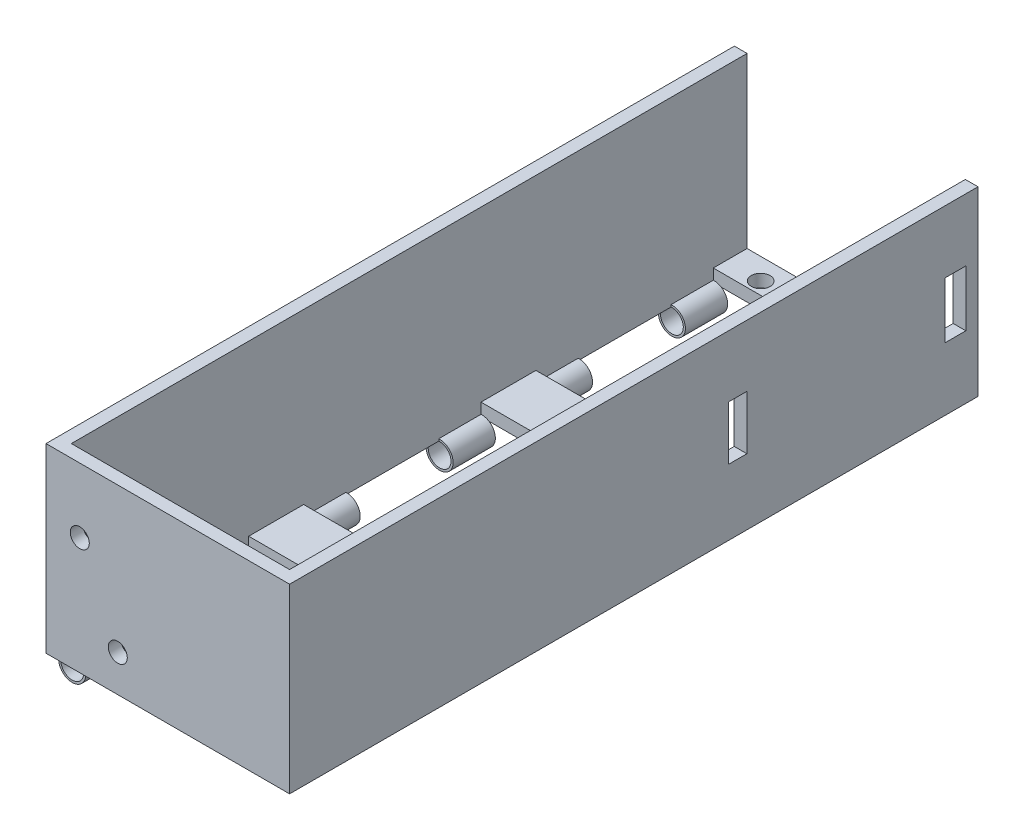
SolidWorks part; units mm, degrees
ref_plane "Front Plane" through (0, 0, 0) normal (0, 0, 1) x (1, 0, 0)
ref_plane "Top Plane" through (0, 0, 0) normal (0, 1, 0) x (1, 0, 0)
ref_plane "Right Plane" through (0, 0, 0) normal (1, 0, 0) x (0, 0, -1)
sketch "Sketch1" plane through (0, 0, 0) normal (0, 0, 1) x (1, 0, 0)
  line L0 (0, 0) -> (0, -10)
  line L1 (0, -10) -> (0, -40)
  line L2 (0, -40) -> (51.6786, -40)
  line L5 (-3, 0) -> (-3, -10)
  line L6 (-3, -10) -> (-3, -43)
  line L7 (-3, -43) -> (54.6786, -43)
  line L10 (-3, 0) -> (0, 0)
  line L12 (51.6786, -40) -> (51.6786, 0)
  line L13 (51.6786, -40) -> (51.6786, 37.6119) construction
  line L14 (51.6786, 37.6119) -> (67.0297, -2.1736) construction
  line L15 (54.6786, -43) -> (54.6786, 21.503) construction
  line L16 (54.6786, 21.503) -> (64.2308, -3.2535) construction
  line L17 (51.6786, 0) -> (54.6786, 0)
  line L18 (54.6786, 0) -> (54.6786, -43)
  dimension "D2" = 10
  dimension "D3" = 30
  dimension "D5" = 3
  dimension "D1" = 3
extrude "Boss-Extrude1" add sketch "Sketch1" along normal blind 160
sketch "Sketch2" plane through (0, 0, 0) normal (0, 1, 0) x (1, 0, 0)
  line L0 (51.6786, -160) -> (0, -160) construction
  line L1 (49, -8) -> (0, -8)
  line L2 (49, -8) -> (49, -50)
  line L3 (49, -50) -> (0, -50)
  line L4 (0, -8) -> (0, -50)
  line L5 (49, -63) -> (0, -63)
  line L6 (49, -63) -> (49, -105)
  line L7 (49, -105) -> (0, -105)
  line L8 (0, -63) -> (0, -105)
  line L9 (49, -118) -> (0, -118)
  line L10 (49, -118) -> (49, -160)
  line L11 (49, -160) -> (0, -160)
  line L12 (0, -118) -> (0, -160)
  line L13 (0, -160) -> (0, 0) construction
  dimension "D1" = 42
  dimension "D2" = 13
  dimension "D3" = 42
  dimension "D4" = 13
  dimension "D5" = 42
  dimension "D6" = 49
extrude "Cut-Extrude1" cut sketch "Sketch2" against normal through all
sketch "Sketch3" plane through (0, 0, 160) normal (0, 0, 1) x (1, 0, 0)
  line L0 (-3, 0) -> (54.6786, 0)
  line L1 (54.6786, 0) -> (54.6786, -43)
  line L2 (54.6786, -43) -> (0, -43)
  line L10 (0, 0) -> (-3, 0)
  line L11 (-3, 0) -> (-3, -43)
  line L13 (-3, -43) -> (0, -43)
  line L18 (0, -43) -> (0, 0)
  line L21 (-3, 0) -> (-3, -43)
  line L23 (-3, -43) -> (0, -43)
  dimension "D1" = 0
extrude "Boss-Extrude2" add sketch "Sketch3" along normal blind 3
sketch "Sketch4" plane through (0, 0, 163) normal (0, 0, 1) x (1, 0, 0)
  circle A0 centre (14, -34.2995) radius 2.25 construction
  circle A1 centre (5, -15.3106) radius 2.25 construction
  circle A2 centre (14, -34.2995) radius 2.25
  circle A3 centre (5, -15.3106) radius 2.25
extrude "Cut-Extrude2" cut sketch "Sketch4" against normal up to next
sketch "Sketch5" plane through (0, -40, 0) normal (0, 1, 0) x (1, 0, 0)
  line L14 (49, -8) -> (49, -50)
  line L15 (49, -50) -> (0, -50)
  line L16 (0, -50) -> (0, -63)
  line L17 (0, -63) -> (49, -63)
  line L18 (49, -63) -> (49, -105)
  line L19 (49, -105) -> (0, -105)
  line L20 (0, -105) -> (0, -118)
  line L21 (0, -118) -> (49, -118)
  line L22 (49, -118) -> (49, -160)
  line L23 (49, -160) -> (51.6786, -160)
  line L24 (51.6786, -160) -> (51.6786, 0)
  line L25 (51.6786, 0) -> (0, 0)
  line L26 (0, 0) -> (0, -8)
  line L27 (0, -8) -> (49, -8)
  line L28 (49, -8) -> (49, -50)
  line L29 (49, -50) -> (0, -50)
  line L30 (0, -50) -> (0, -63)
  line L31 (0, -63) -> (49, -63)
  line L32 (49, -63) -> (49, -105)
  line L33 (49, -105) -> (0, -105)
  line L34 (0, -105) -> (0, -118)
  line L35 (0, -118) -> (49, -118)
  line L36 (49, -118) -> (49, -160)
  line L37 (49, -160) -> (51.6786, -160)
  line L38 (51.6786, -160) -> (51.6786, 0)
  line L39 (51.6786, 0) -> (0, 0)
  line L40 (0, 0) -> (0, -8)
  line L41 (0, -8) -> (49, -8)
  ellipse E0 centre (8.2809, -5.054) end of major axis (6.0309, -5.054) minor radius 2.2278 construction
  ellipse E1 centre (8.2809, -5.054) end of major axis (6.0309, -5.054) minor radius 2.2278
  dimension "D1" = 0
extrude "Cut-Extrude3" cut sketch "Sketch5" against normal up to next contours E1 region at (8.2809, -40, 5.054)
sketch "Sketch6" plane through (0, 0, 160) normal (0, 0, 1) x (1, 0, 0)
  line L0 (-3, 0) -> (-3, -43) construction
  line L4 (6.0309, -43) -> (10.5309, -43) construction
  circle A0 centre (0.2, -45.7) radius 2.7
  circle A1 centre (0.2, -45.7) radius 3.2
  dimension "D1" = 6.4
  dimension "D2" = 5.4
extrude "Boss-Extrude3" add sketch "Sketch6" against normal blind 10
pattern_linear "LPattern1" count 3 spacing 55 along (0, 0, -1) of "Boss-Extrude3"
sketch "Sketch8" plane through (0, 0, 118) normal (0, 0, 1) x (1, 0, 0)
  circle A0 centre (0.2, -45.7) radius 2.7 construction
  arc A1 (-1.5176, -43) -> (0, -42.5063) centre (0.2, -45.7) ccw construction
  circle A2 centre (0.2, -45.7) radius 2.7
  circle A3 centre (0.2, -45.7) radius 3.2
extrude "Boss-Extrude5" add sketch "Sketch8" along normal blind 10
pattern_linear "LPattern4" count 3 spacing 55 along (0, 0, -1) of "Boss-Extrude5"
sketch "Sketch9" plane through (0, -43, 0) normal (0, -1, 0) x (1, 0, 0)
  line L0 (-3, 163) -> (-3, 0) construction
  line L1 (-1.5176, 160) -> (-3, 160)
  line L2 (-1.5176, 160) -> (-1.5176, 150)
  line L3 (-1.5176, 150) -> (-3, 150)
  line L4 (-3, 160) -> (-3, 150)
  line L5 (-3, 150) -> (3.4, 150) construction
  line L6 (-3, 118) -> (3.4, 118) construction
  line L7 (-1.5176, 105) -> (-3, 105)
  line L8 (-1.5176, 105) -> (-1.5176, 95)
  line L9 (-1.5176, 95) -> (-3, 95)
  line L10 (-3, 105) -> (-3, 95)
  line L11 (-1.5176, 128) -> (-3, 128)
  line L12 (-1.5176, 128) -> (-1.5176, 118)
  line L13 (-1.5176, 118) -> (-3, 118)
  line L14 (-3, 128) -> (-3, 118)
  line L15 (-1.5176, 73) -> (-3, 73)
  line L16 (-1.5176, 73) -> (-1.5176, 63)
  line L17 (-1.5176, 63) -> (-3, 63)
  line L18 (-3, 73) -> (-3, 63)
  line L19 (-1.5176, 50) -> (-3, 50)
  line L20 (-1.5176, 50) -> (-1.5176, 40)
  line L21 (-1.5176, 40) -> (-3, 40)
  line L22 (-3, 50) -> (-3, 40)
  line L23 (-1.5176, 18) -> (-3, 18)
  line L24 (-1.5176, 18) -> (-1.5176, 8)
  line L25 (-1.5176, 8) -> (-3, 8)
  line L26 (-3, 18) -> (-3, 8)
  line L27 (-3, 95) -> (3.4, 95) construction
  line L28 (-3, 63) -> (3.4, 63) construction
  line L29 (-3, 40) -> (3.4, 40) construction
extrude "Boss-Extrude6" add sketch "Sketch9" along normal up to next
sketch "Sketch10" plane through (-3, 0, 0) normal (-1, 0, 0) x (0, 0, 1)
  line L0 (128, -45.7) -> (128, -43) construction
  line L1 (122.4, -43) -> (125.4, -43)
  line L2 (122.4, -43) -> (122.4, -48)
  line L3 (122.4, -48) -> (125.4, -48)
  line L4 (125.4, -43) -> (125.4, -48)
  line L5 (122.4, -15.4) -> (125.4, -15.4)
  line L6 (122.4, -15.4) -> (122.4, -20.4)
  line L7 (122.4, -20.4) -> (125.4, -20.4)
  line L8 (125.4, -15.4) -> (125.4, -20.4)
  line L9 (150, -43) -> (128, -43) construction
  dimension "D1" = 2.6
  dimension "D2" = 22.6
  dimension "D3" = 5
  dimension "D4" = 5
  dimension "D5" = 3
  dimension "D6" = 3
extrude "Boss-Extrude7" add sketch "Sketch10" along normal blind 13
pattern_linear "LPattern5" count 3 spacing 55 along (0, 0, -1) of "Boss-Extrude7"
sketch "Sketch11" plane through (0, 0, 125.4) normal (0, 0, 1) x (1, 0, 0)
  circle A0 centre (-9.2, -45.95) radius 1
  circle A1 centre (-9.2, -17.45) radius 1
  dimension "D1" = 2
extrude "Cut-Extrude4" cut sketch "Sketch11" against normal through all
fillet "Fillet1" radius 4 9 edges at (-3, -15.4, 123.9) (-3, -17.9, 122.4) (-3, -44.35, 122.4) (-3, -44.35, 12.4) (-3, -17.9, 12.4) (-3, -15.4, 13.9) (-3, -44.35, 67.4) (-3, -15.4, 68.9) (-3, -17.9, 67.4)
sketch "Sketch12" plane through (0, -40, 0) normal (0, 1, 0) x (1, 0, 0)
  line L1 (32.6182, -9.1719) -> (19.1667, -9.1719)
  line L2 (32.6182, -9.1719) -> (32.6182, -2.8815)
  line L3 (32.6182, -2.8815) -> (19.1667, -2.8815)
  line L4 (19.1667, -9.1719) -> (19.1667, -2.8815)
  line L5 (31.0636, -58.1853) -> (19.4684, -58.1853)
  line L6 (31.0636, -58.1853) -> (31.0636, -53.5298)
  line L7 (31.0636, -53.5298) -> (19.4684, -53.5298)
  line L8 (19.4684, -58.1853) -> (19.4684, -53.5298)
extrude "Cut-Extrude5" cut sketch "Sketch12" against normal through all
sketch "Sketch13" plane through (51.6786, 0, 0) normal (-1, 0, 0) x (0, 0, 1)
  line L1 (2.879, -14.7915) -> (7.8356, -14.7915)
  line L2 (2.879, -14.7915) -> (2.879, -28.0944)
  line L3 (2.879, -28.0944) -> (7.8356, -28.0944)
  line L4 (7.8356, -14.7915) -> (7.8356, -28.0944)
  line L5 (54.7205, -14.5899) -> (59.0899, -14.5899)
  line L6 (54.7205, -14.5899) -> (54.7205, -27.3851)
  line L7 (54.7205, -27.3851) -> (59.0899, -27.3851)
  line L8 (59.0899, -14.5899) -> (59.0899, -27.3851)
  line L9 (50.9179, -252.7121) -> (57.0548, -252.7121)
  line L10 (50.9179, -252.7121) -> (50.9179, -267.8576)
  line L11 (50.9179, -267.8576) -> (57.0548, -267.8576)
  line L12 (57.0548, -252.7121) -> (57.0548, -267.8576)
extrude "Cut-Extrude8" cut sketch "Sketch13" against normal through all
